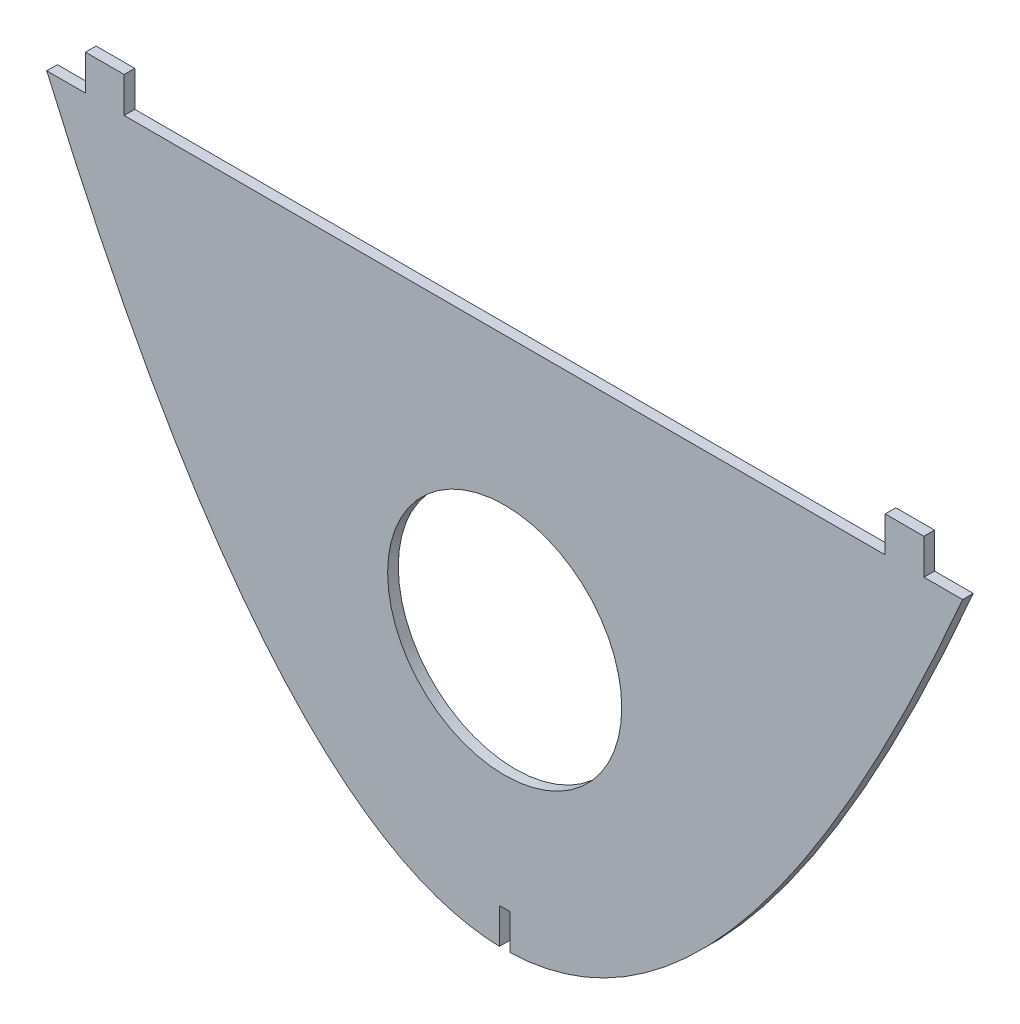
SolidWorks part; units mm, degrees
ref_plane "Front Plane" through (0, 0, 0) normal (0, 0, 1) x (1, 0, 0)
ref_plane "Top Plane" through (0, 0, 0) normal (0, 1, 0) x (1, 0, 0)
ref_plane "Right Plane" through (0, 0, 0) normal (1, 0, 0) x (0, 0, -1)
sketch "Sketch1" plane through (0, 0, 0) normal (0, 0, 1) x (1, 0, 0)
  line L2 (-129.0994, 150) -> (-118.1892, 150)
  line L4 (118.1892, 150) -> (118.1892, 160)
  line L5 (-118.1892, 150) -> (-118.1892, 160)
  line L6 (-118.1892, 160) -> (-107.2791, 160)
  line L7 (-107.2791, 160) -> (-107.2791, 150)
  line L10 (118.1892, 150) -> (129.0994, 150)
  line L11 (118.1892, 160) -> (107.2791, 160)
  line L12 (107.2791, 160) -> (107.2791, 150)
  line L13 (-107.2791, 150) -> (107.2791, 150)
  spline S0 degree 2 poles (-144.7143, 188.48) (0, -188.48) (144.7143, 188.48) knots 0 0 0 1 1 1 construction
  spline S1 degree 2 poles (-129.0994, 150) (0, -150) (129.0994, 150) knots 0.053951 0.053951 0.053951 0.946049 0.946049 0.946049
  point P12 (0, 75)
sketch "Sketch4" plane through (0, 0, 0) normal (0, 0, 1) x (1, 0, 0)
  line L7 (-1.4999, 9.9989) -> (1.5, 9.9989)
  line L8 (-1.4999, 9.9989) -> (-1.4999, 0)
  line L9 (-1.4999, 0) -> (1.5, 0)
  line L10 (1.5, 9.9989) -> (1.5, 0)
extrude "Boss-Extrude1" add sketch "Sketch1" along normal blind 3 contours S1 L10 L4 L11 L12 L13 L7 L6 L5 L2
extrude "Cut-Extrude1" cut sketch "Sketch4" along normal blind 59
sketch "Sketch5" plane through (0, 0, 0) normal (0, 0, 1) x (1, 0, 0)
  circle A0 centre (0, 75.5355) radius 33
  dimension "D1" = 66
extrude "Cut-Extrude2" cut sketch "Sketch5" along normal through all
